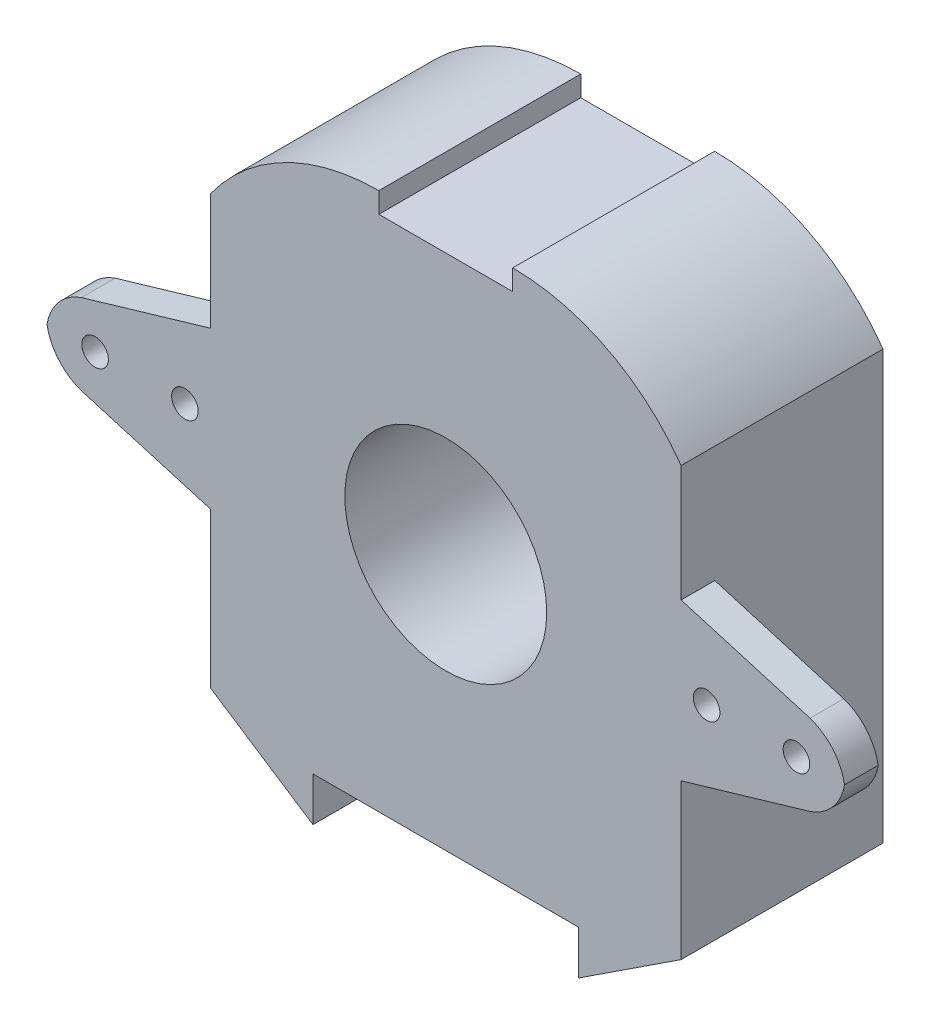
SolidWorks part; units mm, degrees
ref_plane "Front Plane" through (0, 0, 0) normal (0, 0, 1) x (1, 0, 0)
ref_plane "Top Plane" through (0, 0, 0) normal (0, 1, 0) x (1, 0, 0)
ref_plane "Right Plane" through (0, 0, 0) normal (1, 0, 0) x (0, 0, -1)
sketch "Sketch1" plane through (0, 0, 0) normal (0, 0, 1) x (1, 0, 0)
  line L0 (0, 70.9446) -> (0, 19.6997) construction
  line L2 (-17.7635, 14.683) -> (-17.7635, -17.609)
  line L3 (-17.7635, -17.609) -> (-10.0241, -22.6796)
  line L4 (-10.0241, -22.6796) -> (-10.0241, -19.3595)
  line L5 (-10.0241, -19.3595) -> (10.0241, -19.3595)
  line L6 (-5.0511, 21.2507) -> (-5.0511, 19.6997)
  line L7 (-5.0511, 19.6997) -> (5.0511, 19.6997)
  line L8 (10.0241, -22.6796) -> (10.0241, -19.3595)
  line L9 (17.7635, -17.609) -> (10.0241, -22.6796)
  line L10 (17.7635, 14.683) -> (17.7635, -17.609)
  line L11 (5.0511, 21.2507) -> (5.0511, 19.6997)
  line L13 (0, 19.6997) -> (0, -83.3132) construction
  arc A0 (-5.0511, 21.2507) -> (-17.7635, 14.683) centre (-5.0511, 5.6637) ccw
  arc A1 (5.0511, 21.2507) -> (17.7635, 14.683) centre (5.0511, 5.6637) cw
  point P17 (0, -19.3595)
  point P21 (0, 19.6997)
  point P24 (0, 0)
extrude "Boss-Extrude2" add sketch "Sketch1" along normal blind 15.24
sketch "Sketch5" plane through (0, 0, 15.24) normal (0, 0, 1) x (1, 0, 0)
  circle A0 centre (0, 0) radius 7.62
  dimension "D1" = 15.24
extrude "Cut-Extrude2" cut sketch "Sketch5" against normal blind 15.24
sketch "Sketch6" plane through (0, 0, 15.24) normal (0, 0, 1) x (1, 0, 0)
  line L2 (-27.4971, 3.0373) -> (-17.7635, 5.9001)
  line L3 (-17.7635, 14.683) -> (-17.7635, -17.609) construction
  line L4 (-17.7635, 5.9001) -> (-17.7635, -5.921)
  line L5 (-27.4971, -3.0582) -> (-17.7635, -5.921)
  line L6 (0, 24.5613) -> (0, -29.2199) construction
  line L7 (27.4971, 3.0373) -> (17.7635, 5.9001)
  line L8 (27.4971, -3.0582) -> (17.7635, -5.921)
  line L9 (17.7635, 5.9001) -> (17.7635, -5.921)
  arc A0 (-27.4971, 3.0373) -> (-30.1001, -0.0104) centre (-26.2297, -0.6805) ccw
  arc A1 (-27.4971, -3.0582) -> (-30.1001, -0.0104) centre (-26.2297, 0.6596) cw
  arc A2 (27.4971, 3.0373) -> (30.1001, -0.0104) centre (26.2297, -0.6805) cw
  arc A3 (27.4971, -3.0582) -> (30.1001, -0.0104) centre (26.2297, 0.6596) ccw
  point P3 (-19.5103, 9.4005)
extrude "Boss-Extrude3" add sketch "Sketch6" against normal blind 2.54
sketch "Sketch7" plane through (0, 0, 0) normal (0, 0, -1) x (-1, 0, 0)
  line L0 (-34.7295, 0) -> (42.0609, 0) construction
  line L1 (0, 25.6042) -> (0, -30.1557) construction
  circle A0 centre (-19.6881, 0) radius 1.0033
  circle A1 centre (-26.4688, 0) radius 1.0033
  circle A2 centre (19.6881, 0) radius 1.0033
  circle A3 centre (26.4688, 0) radius 1.0033
  dimension "D1" = 2.0066
  dimension "D2" = 2.0066
extrude "Cut-Extrude5" cut sketch "Sketch7" along normal through all both and the other way through all
